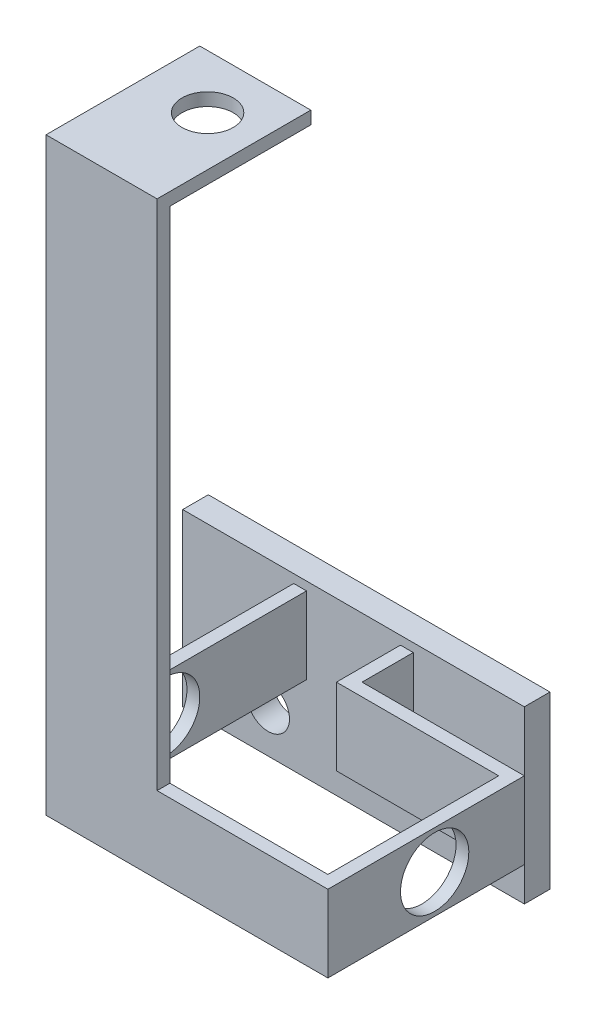
SolidWorks part; units mm, degrees
ref_plane "Front Plane" through (0, 0, 0) normal (0, 0, 1) x (1, 0, 0)
ref_plane "Top Plane" through (0, 0, 0) normal (0, 1, 0) x (1, 0, 0)
ref_plane "Right Plane" through (0, 0, 0) normal (1, 0, 0) x (0, 0, -1)
sketch "Sketch1" plane through (0, 0, 0) normal (0, 0, 1) x (1, 0, 0)
  line L0 (20, 0) -> (20, 44.0735) construction
  line L1 (0, 0) -> (40, 0)
  line L2 (0, 0) -> (0, 20)
  line L3 (0, 20) -> (40, 20)
  line L4 (40, 0) -> (40, 20)
  line L5 (27, 19) -> (27, 10)
  line L6 (27, 19) -> (13, 19)
  line L7 (20, 19) -> (20, 10)
  line L8 (27, 10) -> (13, 10)
  line L9 (13, 19) -> (13, 10)
  circle A0 centre (10, 5) radius 2.5
  circle A1 centre (30, 5) radius 2.5
  point P16 (20, 20)
  dimension "D3" = 5
  dimension "D1" = 40
  dimension "D2" = 20
  dimension "D4" = 10
  dimension "D5" = 20
  dimension "D6" = 5
  dimension "D7" = 7
  dimension "D8" = 9
  dimension "D9" = 10
extrude "Boss-Extrude2" add sketch "Sketch1" along normal blind 32 contours L8 L5 L6 L7 | L6 L9 L8 L7 region at (23.5, 14.5, 0) region at (16.5, 14.5, 0)
extrude "Boss-Extrude3" add sketch "Sketch1<4>" along normal blind 3 contours L1 L0 L8 L9 L6 L3 L2 A0 | L0 L1 L4 L3 L6 L5 L8 A1 region at (8.7097, 9.4161, 0) region at (31.2903, 9.4161, 0)
sketch "Sketch1<4>" plane through (0, 0, 0) normal (0, 0, 1) x (1, 0, 0) same geometry as "Sketch1"
sketch "Sketch3" plane through (0, 19, 0) normal (0, 1, 0) x (1, 0, 0)
  line L0 (13, -32) -> (13, -3) construction
  line L2 (14.5, -3) -> (14.5, -30.5)
  line L3 (14.5, -30.5) -> (25.5, -30.5)
  line L4 (25.5, -3) -> (25.5, -30.5)
  line L5 (27, -32) -> (13, -32) construction
  line L6 (27, -32) -> (27, -3) construction
  line L8 (27, -3) -> (13, -3) construction
  line L9 (14.5, -3) -> (25.5, -3)
  dimension "D1" = 1.5
  dimension "D2" = 1.5
  dimension "D3" = 1.5
extrude "Cut-Extrude1" cut sketch "Sketch3" against normal through all both and the other way through all
sketch "Sketch6" plane through (27, 0, 0) normal (1, 0, 0) x (0, 0, -1)
  line L0 (-32, 10) -> (-3, 10) construction
  line L1 (-32, 19) -> (-9, 19)
  line L2 (-32, 19) -> (-32, 10)
  line L3 (-32, 10) -> (-9, 10)
  line L4 (-9, 19) -> (-9, 10)
  line L5 (-3, 19) -> (-3, 10) construction
  dimension "D1" = 6
extrude "Boss-Extrude4" add sketch "Sketch6" along normal blind 19
sketch "Sketch9" plane through (0, 19, 0) normal (0, 1, 0) x (1, 0, 0)
  line L0 (46, -9) -> (27, -9) construction
  line L1 (25.5, -10.5) -> (44.5, -10.5)
  line L2 (25.5, -10.5) -> (25.5, -30.5)
  line L3 (25.5, -30.5) -> (44.5, -30.5)
  line L4 (44.5, -10.5) -> (44.5, -30.5)
  line L5 (46, -9) -> (46, -32) construction
  line L6 (46, -32) -> (13, -32) construction
  line L7 (25.5, -3) -> (25.5, -30.5) construction
  dimension "D1" = 1.5
  dimension "D2" = 1.5
  dimension "D3" = 1.5
  dimension "D4" = 0
extrude "Cut-Extrude3" cut sketch "Sketch9" against normal through all both and the other way through all
sketch "Sketch12" plane through (13, 0, 0) normal (-1, 0, 0) x (0, 0, 1)
  line L0 (3, 19) -> (3, 10) construction
  line L1 (32, 10) -> (3, 10) construction
  line L2 (32, 19) -> (32, 10) construction
  circle A0 centre (19.5, 14.5) radius 4
  dimension "D1" = 8
  dimension "D2" = 4.5
  dimension "6.5" = 16.5
  dimension "D3" = 12.5
extrude "Cut-Extrude4" cut sketch "Sketch12" against normal through all both and the other way through all
sketch "Sketch14" plane through (0, 19, 0) normal (0, 1, 0) x (1, 0, 0)
  line L11 (13, -32) -> (26, -32)
  line L12 (13, -32) -> (13, -22)
  line L13 (13, -22) -> (26, -22)
  line L14 (26, -32) -> (26, -22)
  dimension "D1" = 10
  dimension "D2" = 13
extrude "Boss-Extrude6" add sketch "Sketch14" along normal blind 60
sketch "Sketch17" plane through (0, 19, 0) normal (0, -1, 0) x (1, 0, 0)
  line L0 (14.5, 30.5) -> (26, 30.5) construction
  line L1 (14.5, 30.5) -> (26, 30.5)
  line L2 (14.5, 30.5) -> (14.5, 22)
  line L3 (14.5, 22) -> (26, 22)
  line L4 (26, 30.5) -> (26, 22)
  line L5 (14.5, 30.5) -> (14.5, 22) construction
extrude "Cut-Extrude6" cut sketch "Sketch17" against normal offset from surface (58.5 mm away) 1.5 up to face at (19.5, 79, 27)
sketch "Sketch18" plane through (0, 0, 22) normal (0, 0, -1) x (-1, 0, 0)
  line L0 (-13, 79) -> (-13, 19) construction
  line L1 (-26, 79) -> (-13, 79)
  line L2 (-26, 79) -> (-26, 77.5)
  line L3 (-26, 77.5) -> (-13, 77.5)
  line L4 (-13, 79) -> (-13, 77.5)
  dimension "D1" = 1.5
extrude "Boss-Extrude7" add sketch "Sketch18" along normal blind 8
sketch "Sketch19" plane through (0, 79, 0) normal (0, 1, 0) x (1, 0, 0)
  line L0 (14.5, -31.9005) -> (14.5, -14.3427) construction
  line L1 (13, -14) -> (13, -32) construction
  circle A0 centre (20.2199, -20.303) radius 3
  dimension "D2" = 6
  dimension "D1" = 1.5
extrude "Cut-Extrude7" cut sketch "Sketch19" against normal blind 1.5
sketch "Sketch20" plane through (14.5, 0, 0) normal (1, 0, 0) x (0, 0, -1)
  line L0 (-22, 77.5) -> (-22, 19) construction
  line L1 (-30.5, 77.5) -> (-22, 77.5)
  line L2 (-30.5, 77.5) -> (-30.5, 42.5)
  line L3 (-30.5, 42.5) -> (-22, 42.5)
  line L4 (-22, 77.5) -> (-22, 42.5)
  dimension "D1" = 35
extrude "Cut-Extrude8" cut sketch "Sketch20" against normal blind 1.5
fillet "Fillet1" radius 10 1 edges at (13.75, 42.5, 30.5)
